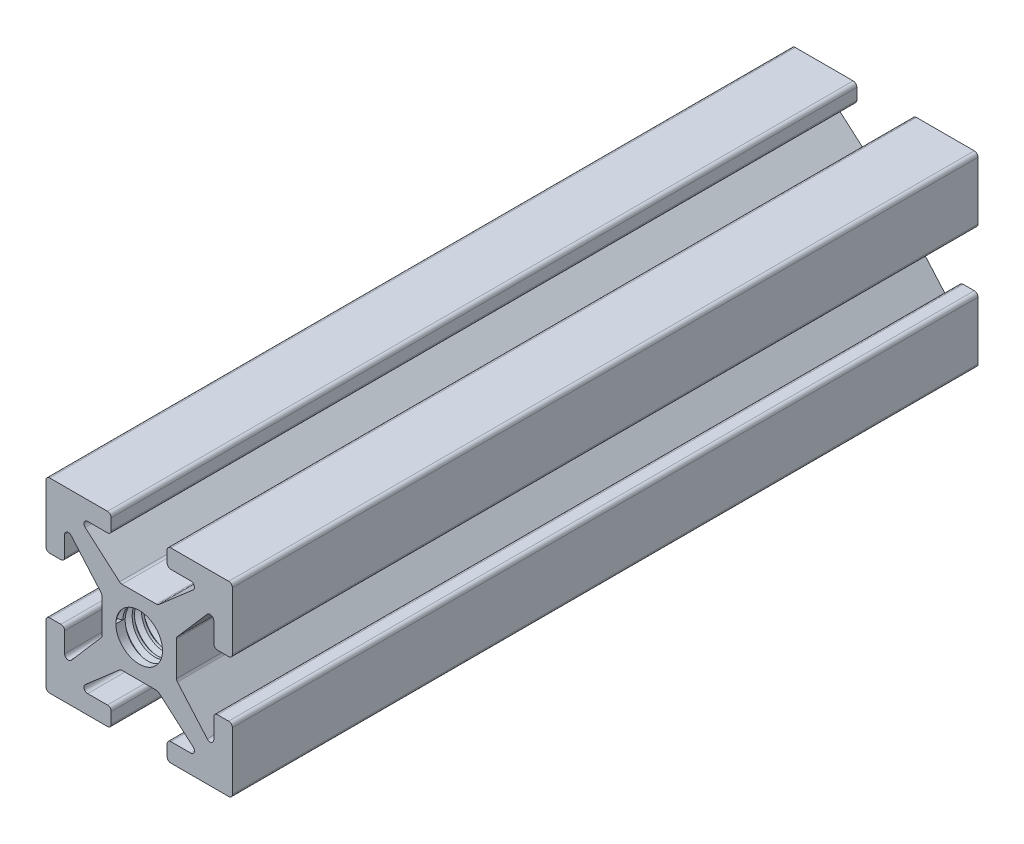
SolidWorks part; units mm, degrees
ref_plane "Front Plane" through (0, 0, 0) normal (0, 0, 1) x (1, 0, 0)
ref_plane "Top Plane" through (0, 0, 0) normal (0, 1, 0) x (1, 0, 0)
ref_plane "Right Plane" through (0, 0, 0) normal (1, 0, 0) x (0, 0, -1)
sketch "Sketch1" plane through (0, 0, 0) normal (0, 0, 1) x (1, 0, 0)
  line L1 (5, -5) -> (-5, -5) construction
  line L2 (5, -5) -> (5, 5) construction
  line L3 (5, 5) -> (-5, 5) construction
  line L4 (-5, -5) -> (-5, 5) construction
  line L5 (5, -5) -> (-5, 5) construction
  line L6 (5, 5) -> (-5, -5) construction
  line L42 (-4.8, 1.5) -> (-4.2, 1.5)
  line L43 (-5, 4.8) -> (-5, 1.7)
  line L44 (-4, 1.7) -> (-4, 2.7652)
  line L45 (-3.6491, 2.8964) -> (-2.0491, 1.0564)
  line L46 (1.5, 4.8) -> (1.5, 4.2)
  line L47 (2, -2) -> (-2, -2) construction
  line L48 (2, -2) -> (2, 2) construction
  line L49 (2, 2) -> (-2, 2) construction
  line L50 (-2, -2) -> (-2, 2) construction
  line L51 (2, -2) -> (-2, 2) construction
  line L52 (2, 2) -> (-2, -2) construction
  line L53 (4.8, 5) -> (1.7, 5)
  line L54 (1.7, 4) -> (2.7652, 4)
  line L55 (2.8964, 3.6491) -> (1.0564, 2.0491)
  line L56 (0, 5) -> (0, -5) construction
  line L61 (-5, 0) -> (5, 0) construction
  line L62 (0.9252, 2) -> (0, 2) construction
  line L63 (2, 0.9252) -> (2, 0) construction
  line L64 (-2, 0.9252) -> (-2, 0) construction
  line L65 (-0.9252, 2) -> (0, 2) construction
  line L66 (-2.8964, 3.6491) -> (-1.0564, 2.0491)
  line L67 (-1.7, 4) -> (-2.7652, 4)
  line L68 (-1.5, 4.8) -> (-1.5, 4.2)
  line L69 (-4.8, 5) -> (-1.7, 5)
  line L70 (3.6491, 2.8964) -> (2.0491, 1.0564)
  line L71 (4, 1.7) -> (4, 2.7652)
  line L72 (4.8, 1.5) -> (4.2, 1.5)
  line L73 (5, 4.8) -> (5, 1.7)
  line L74 (4.8, -1.5) -> (4.2, -1.5)
  line L75 (5, -4.8) -> (5, -1.7)
  line L76 (4, -1.7) -> (4, -2.7652)
  line L77 (3.6491, -2.8964) -> (2.0491, -1.0564)
  line L78 (2, -0.9252) -> (2, 0) construction
  line L79 (0.9252, -2) -> (0, -2) construction
  line L80 (2.8964, -3.6491) -> (1.0564, -2.0491)
  line L81 (1.7, -4) -> (2.7652, -4)
  line L82 (1.5, -4.8) -> (1.5, -4.2)
  line L83 (4.8, -5) -> (1.7, -5)
  line L84 (-1.5, -4.8) -> (-1.5, -4.2)
  line L85 (-4.8, -5) -> (-1.7, -5)
  line L86 (-1.7, -4) -> (-2.7652, -4)
  line L87 (-2.8964, -3.6491) -> (-1.0564, -2.0491)
  line L88 (-0.9252, -2) -> (0, -2) construction
  line L89 (-2, -0.9252) -> (-2, 0) construction
  line L90 (-3.6491, -2.8964) -> (-2.0491, -1.0564)
  line L91 (-4, -1.7) -> (-4, -2.7652)
  line L92 (-4.8, -1.5) -> (-4.2, -1.5)
  line L93 (-5, -4.8) -> (-5, -1.7)
  line L94 (-2, 0.9252) -> (-2, -0.9252)
  line L95 (-0.9252, -2) -> (0.9252, -2)
  line L96 (2, -0.9252) -> (2, 0.9252)
  line L97 (2, 0.9252) -> (2, -0.9252)
  line L98 (0.9252, 2) -> (-0.9252, 2)
  arc A37 (-4.2, 1.5) -> (-4, 1.7) centre (-4.2, 1.7) ccw
  arc A38 (-2, 0.9252) -> (-2.0491, 1.0564) centre (-2.2, 0.9252) ccw
  arc A39 (-3.6491, 2.8964) -> (-4, 2.7652) centre (-3.8, 2.7652) ccw
  arc A40 (-4.8, 1.5) -> (-5, 1.7) centre (-4.8, 1.7) cw
  arc A41 (-0.9252, 2) -> (-1.0564, 2.0491) centre (-0.9252, 2.2) cw
  arc A42 (-2.8964, 3.6491) -> (-2.7652, 4) centre (-2.7652, 3.8) cw
  arc A43 (-1.5, 4.2) -> (-1.7, 4) centre (-1.7, 4.2) cw
  arc A44 (-1.5, 4.8) -> (-1.7, 5) centre (-1.7, 4.8) ccw
  arc A45 (1.5, 4.2) -> (1.7, 4) centre (1.7, 4.2) ccw
  arc A46 (0.9252, 2) -> (1.0564, 2.0491) centre (0.9252, 2.2) ccw
  arc A47 (2.8964, 3.6491) -> (2.7652, 4) centre (2.7652, 3.8) ccw
  arc A48 (1.5, 4.8) -> (1.7, 5) centre (1.7, 4.8) cw
  arc A49 (2, 0.9252) -> (2.0491, 1.0564) centre (2.2, 0.9252) cw
  arc A50 (3.6491, 2.8964) -> (4, 2.7652) centre (3.8, 2.7652) cw
  arc A51 (4.2, 1.5) -> (4, 1.7) centre (4.2, 1.7) cw
  arc A52 (4.8, 1.5) -> (5, 1.7) centre (4.8, 1.7) ccw
  arc A53 (4.2, -1.5) -> (4, -1.7) centre (4.2, -1.7) ccw
  arc A54 (2, -0.9252) -> (2.0491, -1.0564) centre (2.2, -0.9252) ccw
  arc A55 (3.6491, -2.8964) -> (4, -2.7652) centre (3.8, -2.7652) ccw
  arc A56 (4.8, -1.5) -> (5, -1.7) centre (4.8, -1.7) cw
  arc A57 (0.9252, -2) -> (1.0564, -2.0491) centre (0.9252, -2.2) cw
  arc A58 (2.8964, -3.6491) -> (2.7652, -4) centre (2.7652, -3.8) cw
  arc A59 (1.5, -4.2) -> (1.7, -4) centre (1.7, -4.2) cw
  arc A60 (1.5, -4.8) -> (1.7, -5) centre (1.7, -4.8) ccw
  arc A61 (-1.5, -4.2) -> (-1.7, -4) centre (-1.7, -4.2) ccw
  arc A62 (-0.9252, -2) -> (-1.0564, -2.0491) centre (-0.9252, -2.2) ccw
  arc A63 (-2.8964, -3.6491) -> (-2.7652, -4) centre (-2.7652, -3.8) ccw
  arc A64 (-1.5, -4.8) -> (-1.7, -5) centre (-1.7, -4.8) cw
  arc A65 (-2, -0.9252) -> (-2.0491, -1.0564) centre (-2.2, -0.9252) cw
  arc A66 (-3.6491, -2.8964) -> (-4, -2.7652) centre (-3.8, -2.7652) cw
  arc A67 (-4.2, -1.5) -> (-4, -1.7) centre (-4.2, -1.7) cw
  arc A68 (-4.8, -1.5) -> (-5, -1.7) centre (-4.8, -1.7) ccw
  arc A69 (-5, -4.8) -> (-4.8, -5) centre (-4.8, -4.8) ccw
  arc A70 (4.8, -5) -> (5, -4.8) centre (4.8, -4.8) ccw
  arc A71 (5, 4.8) -> (4.8, 5) centre (4.8, 4.8) ccw
  arc A72 (-5, 4.8) -> (-4.8, 5) centre (-4.8, 4.8) cw
  circle A73 centre (0, 0) radius 1.5 construction
  circle A74 centre (0, 0) radius 1.25
  point P0 (0, 0)
  point P9 (0, 0)
  point P15 (0, 0)
  point P38 (0, 0)
  point P44 (0, 0)
  point P67 (0, 0)
  point P73 (0, 0)
  point P96 (0, 0)
  point P118 (0, 0)
  point P139 (-4, 1.5)
  point P142 (-2, 1)
  point P145 (-4, 3.3)
  point P148 (-5, 1.5)
  dimension "D2" = 3.5
  dimension "D7" = 0.2
  dimension "D8" = 0.2
  dimension "D9" = 0.2
  dimension "D10" = 0.2
  dimension "D12" = 0.2
  dimension "D13" = 0.2
  dimension "D14" = 0.2
  dimension "D15" = 0.2
  dimension "D16" = 3
  dimension "D17" = 2.5
  dimension "D1" = 10
  dimension "D3" = 4
  dimension "D4" = 1
  dimension "D5" = 1
  dimension "D6" = 1.8
  dimension "D11" = 4
extrude "Boss-Extrude1" add sketch "Sketch1" along normal mid plane 40 contours A72 L43 A40 L42 A37 L44 A39 L45 A38 L94 A65 L90 A66 L91 A67 L92 A68 L93 A69 L85 A64 L84 A61 L86 A63 L87 A62 L95 A57 L80 A58 L81 A59 L82 A60 L83 A70 L75 A56 L74 A53 L76 A55 L77 A54 L96 A49 L70 A50 L71 A51 | A73 A74 region at (-4.8414, 1.6586, 0)
thread "Thread1" pitch 0.5 method cut profile "Thread Profile1" start angle 0, offset 0, length 8, pitch 0.5, diameter 2.5
ref_plane "Plane1" through (-1.25, 0, 20) normal (0, -1, 0) x (-1, 0, 0)
sketch "Thread Profile1" plane through (-1.25, 0, 20) normal (0, -1, 0) x (-1, 0, 0)
  line L0 (0, 0) -> (0, 0.5) construction
  line L1 (0, 0) -> (0.2706, 0.1562)
  line L2 (0.2706, 0.1562) -> (0.2706, 0.2187)
  line L3 (0.2706, 0.2187) -> (0, 0.375)
  line L4 (0.2706, 0.1875) -> (0, 0.1875) construction
  line L11 (0, 0) -> (0, 0.375)
  point P2 (0, 0)
  dimension "Pitch" = 0.5
  dimension "Profile_Angle" = 60
  dimension "Profile_Land" = 0.0625
  dimension "Profile_Height" = 0.2706
thread "Thread2" pitch 0.5 method cut profile "Thread Profile2" start angle 0, offset 0, length 8, pitch 0.5, diameter 2.5
ref_plane "Plane2" through (1.25, 0, -20) normal (0, -1, 0) x (1, 0, 0)
sketch "Thread Profile2" plane through (1.25, 0, -20) normal (0, -1, 0) x (1, 0, 0)
  line L0 (0, 0) -> (0, 0.5) construction
  line L1 (0, 0) -> (0.2706, 0.1562)
  line L2 (0.2706, 0.1562) -> (0.2706, 0.2187)
  line L3 (0.2706, 0.2187) -> (0, 0.375)
  line L4 (0.2706, 0.1875) -> (0, 0.1875) construction
  line L11 (0, 0) -> (0, 0.375)
  point P2 (0, 0)
  dimension "Pitch" = 0.5
  dimension "Profile_Angle" = 60
  dimension "Profile_Land" = 0.0625
  dimension "Profile_Height" = 0.2706
equation "\"length\"= 40mm"
equation "\"D1@Boss-Extrude1\"=\"length\""
